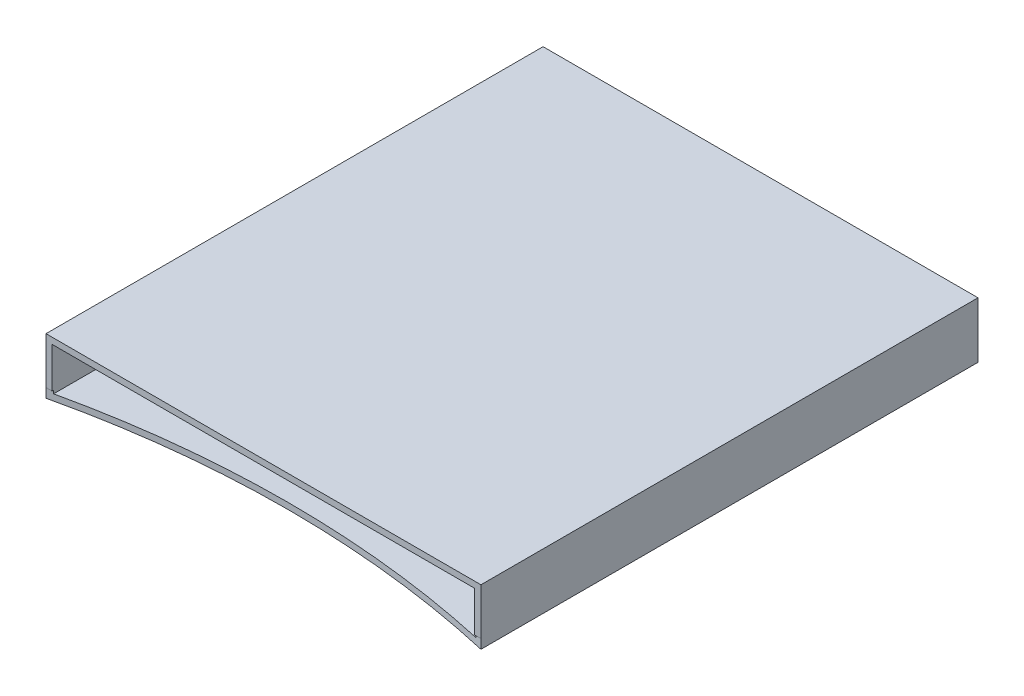
SolidWorks part; units mm, degrees
ref_plane "前视基准面" through (0, 0, 0) normal (0, 0, 1) x (1, 0, 0)
ref_plane "上视基准面" through (0, 0, 0) normal (0, 1, 0) x (1, 0, 0)
ref_plane "右视基准面" through (0, 0, 0) normal (1, 0, 0) x (0, 0, -1)
sketch "草图1" plane through (0, 0, 0) normal (0, 1, 0) x (1, 0, 0)
  line L0 (-42.7555, 0) -> (52.7621, 0) construction
  line L1 (-7, 8) -> (7, 8)
  line L2 (-7, 8) -> (-7, -8)
  line L3 (-7, -8) -> (7, -8)
  line L4 (7, 8) -> (7, -8)
  line L5 (0, 37.6006) -> (0, -33.9618) construction
  dimension "D1" = 14
  dimension "D2" = 16
extrude "拉伸1" add sketch "草图1" along normal blind 1.8
shell "抽壳1" thickness 0.2 removed face at (0, 0.9, 8)
sketch "草图2" plane through (0, 0, 0) normal (0, -1, 0) x (1, 0, 0)
  line L0 (0, 9.8052) -> (0, -10.1985) construction
  line L1 (7, 8) -> (-7, 8)
  arc A0 (7, 8) -> (-7, 8) centre (0, 38.522) cw
extrude "切除-拉伸2" cut sketch "草图2" against normal blind 0.3
